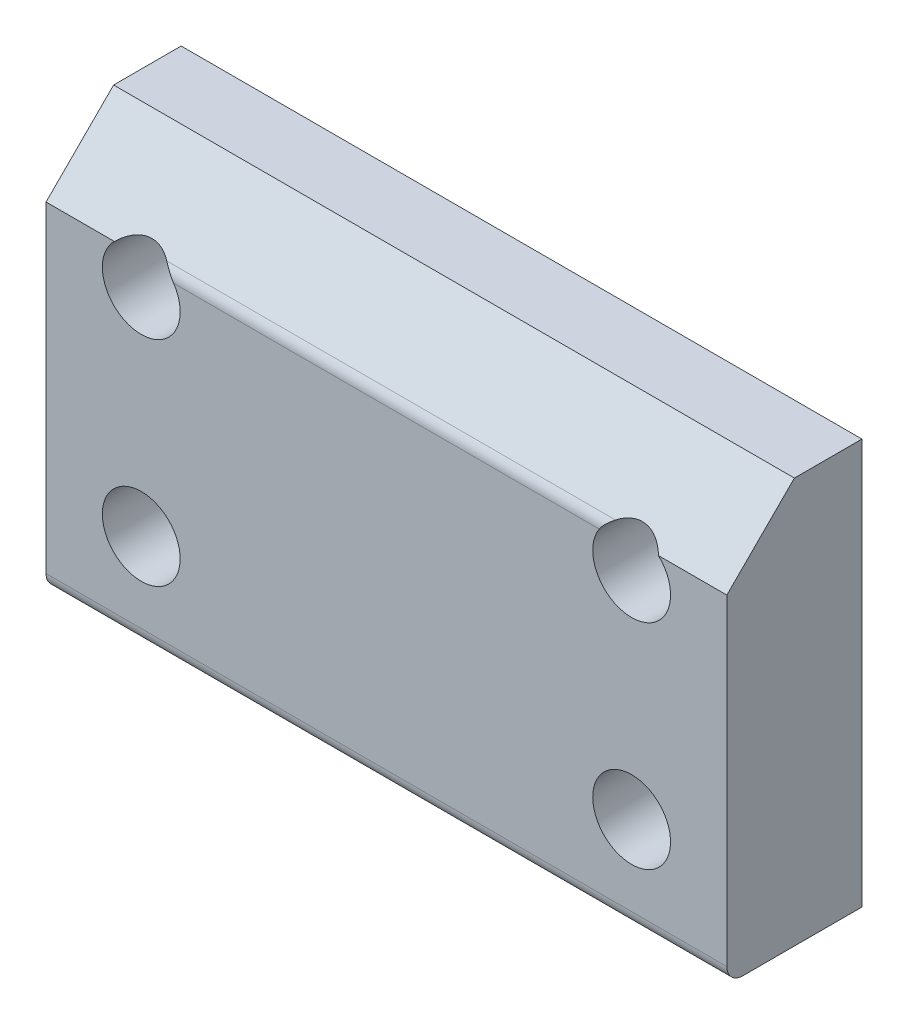
SolidWorks part; units mm, degrees
note: '?' marks a value the reader was unsure of.
material "6061-T6 (SS)"
ref_plane "Front" through (0, 0, 0) normal (0, 0, 1) x (1, 0, 0)
ref_plane "Top" through (0, 0, 0) normal (0, 1, 0) x (1, 0, 0)
ref_plane "Right" through (0, 0, 0) normal (1, 0, 0) x (0, 0, -1)
ref_axis "side-side" through (80.9, 0, 0) along (-1, 0, 0)?
ref_axis "up-down" through (0, 50, 0) along (0, -1, 0)?
ref_axis "front-back" through (0, 0, -80.9) along (0, 0, 1)?
sketch "Sketch1" plane through (0, 0, 0) normal (1, 0, 0) x (0, 0, -1)
  line L0 (0, 6.35) -> (3.175, 9.525)
  line L1 (3.175, 9.525) -> (6.35, 9.525)
  line L2 (0, 6.35) -> (0, -9.525)
  line L3 (0, -9.525) -> (6.35, -9.525)
  line L4 (6.35, 9.525) -> (6.35, -9.525)
  point P0 (6.35, 0)
  dimension "D1" = 6.35
  dimension "D2" = 19.05
  dimension "D3" = 45
  dimension "D4" = 3.175
extrude "Boss-Extrude1" add sketch "Sketch1" along normal mid plane 32
hole_wizard "CBORE for #6 Socket Head Cap Screw1" positions "Sketch3" profile "Sketch5" counterbore size "#6" standard "ANSI Inch"
sketch "Sketch3" plane through (0, 0, -6.35) normal (0, 0, -1) x (-1, 0, 0)
  line L0 (-9.525, 9.525) -> (-9.525, -9.525) construction
  line L1 (-16, 9.525) -> (16, 9.525) construction
  line L2 (-16, -9.525) -> (16, -9.525) construction
  line L3 (0, 0) -> (0, 16.0303) construction
  point P7 (-11.525, 5.025)
  point P9 (-11.525, -5.025)
  point P11 (11.525, 5.025)
  point P13 (11.525, -5.025)
  dimension "D1" = 9.525
  dimension "D2" = 4.5
  dimension "D3" = 4.5
  dimension "D4" = 2
  dimension "D5" = 23.05
sketch "Sketch5" plane through (-11.525, -5.025, -6.35) normal (1, 0, 0) x (0, 1, 0)
  line L0 (0, 0) -> (0, 10.4969)
  line L1 (0, 10.4969) -> (1.8288, 9.398)
  line L2 (1.8288, 9.398) -> (1.8288, 2.54)
  line L3 (1.8288, 2.54) -> (3.5725, 2.54)
  line L4 (3.5725, 2.54) -> (3.5725, 0)
  line L5 (3.5725, 0) -> (0, 0)
  line L10 (0, 10.4969) -> (-1.8288, 9.398) construction
  line L11 (0, -6.35) -> (0, 107.95) construction
  dimension "Hole Dia." = 3.6576
  dimension "Hole Depth" = 9.398
  dimension "C'Bore Dia." = 7.145
  dimension "C'Bore Depth" = 2.54
  dimension "Drill Angle" = 118
hole_wizard "#6 Clearance Hole1" [suppressed] positions "Sketch6" profile "Sketch7" hole size "#6" standard "ANSI Inch"
sketch "Sketch6" plane through (0, -9.525, 0) normal (0, -1, 0) x (-1, 0, 0)
  line L0 (-21, 0) -> (21, 0) construction
  line L2 (0, 0) -> (0, 28.1383) construction
  line L3 (-21, 0) -> (-21, 6.35) construction
  point P0 (-15.525, 0)
  point P7 (15.525, 0)
  dimension "D1" = 4
  dimension "D2" = 5.475
  dimension "D3" = 31.05
  dimension "D4" = 6
sketch "Sketch7" plane through (15.525, -9.525, 0) normal (1, 0, 0) x (0, 0, -1)
  line L0 (0, 0) -> (0, 19.05)
  line L1 (0, 19.05) -> (1.8288, 19.05)
  line L2 (1.8288, 19.05) -> (1.8288, 0)
  line L5 (1.8288, 0) -> (0, 0)
  line L11 (0, -6.35) -> (0, 107.95) construction
  dimension "Thru Hole Dia." = 3.6576
  dimension "Thru Hole Depth" = 19.05
fillet "Fillet1" radius 0.75 2 edges at (0, 6.35, 0) (0, -9.525, 0)
